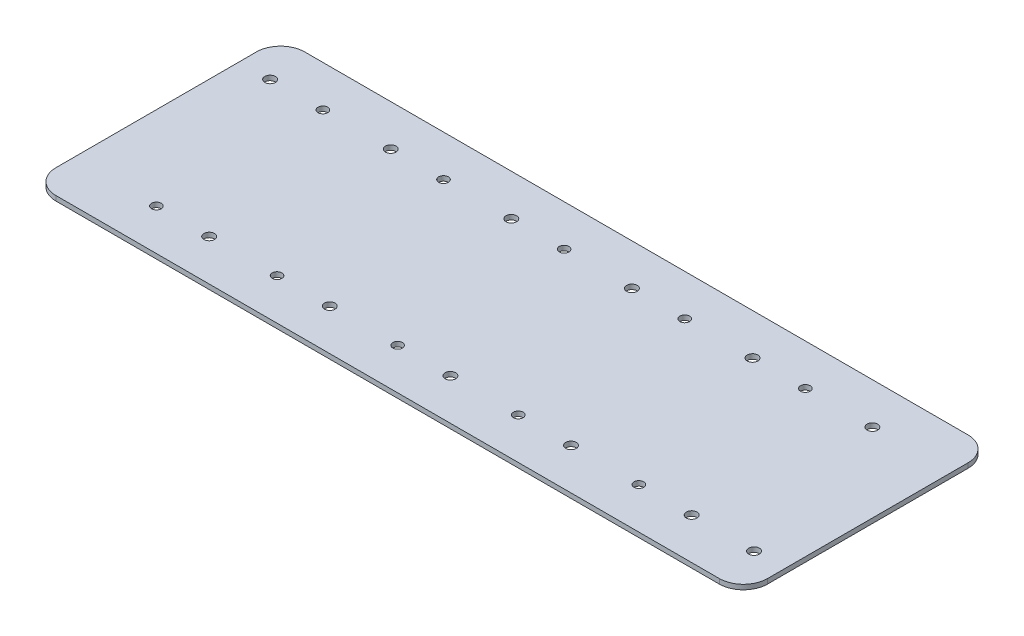
SolidWorks part; units mm, degrees
ref_plane "Front Plane" through (0, 0, 0) normal (0, 0, 1) x (1, 0, 0)
ref_plane "Top Plane" through (0, 0, 0) normal (0, 1, 0) x (1, 0, 0)
ref_plane "Right Plane" through (0, 0, 0) normal (1, 0, 0) x (0, 0, -1)
sketch "Sketch1" plane through (0, 0, 0) normal (0, 1, 0) x (1, 0, 0)
  line L1 (-118, -41.25) -> (118, -41.25)
  line L2 (-118, -41.25) -> (-118, 41.25)
  line L3 (-118, 41.25) -> (118, 41.25)
  line L4 (118, -41.25) -> (118, 41.25)
  line L5 (-118, -41.25) -> (118, 41.25) construction
  line L6 (-118, 41.25) -> (118, -41.25) construction
  point P0 (0, 0)
  dimension "D1" = 236
  dimension "D2" = 82.5
extrude "Boss-Extrude1" add sketch "Sketch1" along normal blind 1.6
fillet "Fillet1" radius 8 4 edges at (118, 0.8, -41.25) (118, 0.8, 41.25) (-118, 0.8, -41.25) (-118, 0.8, 41.25)
sketch "Sketch2" plane through (0, 1.6, 0) normal (0, 1, 0) x (1, 0, 0)
  circle A0 centre (-90.3251, 27.6) radius 1.6
  circle A1 centre (-90.3251, -27.6) radius 1.6
  circle A2 centre (-72.8251, -27.6) radius 1.75
  circle A3 centre (-107.8251, 27.6) radius 1.75
  circle A4 centre (-67.8251, 27.6) radius 1.75
  circle A5 centre (-50.3251, 27.6) radius 1.6
  circle A6 centre (-27.8251, 27.6) radius 1.75
  circle A7 centre (-10.3251, 27.6) radius 1.6
  circle A8 centre (12.1749, 27.6) radius 1.75
  circle A9 centre (29.6749, 27.6) radius 1.6
  circle A10 centre (52.1749, 27.6) radius 1.75
  circle A11 centre (-50.3251, -27.6) radius 1.6
  circle A12 centre (-32.8251, -27.6) radius 1.75
  circle A13 centre (-10.3251, -27.6) radius 1.6
  circle A14 centre (7.1749, -27.6) radius 1.75
  circle A15 centre (29.6749, -27.6) radius 1.6
  circle A16 centre (47.1749, -27.6) radius 1.75
  circle A17 centre (69.6749, -27.6) radius 1.6
  circle A18 centre (87.1749, -27.6) radius 1.75
  circle A19 centre (69.6749, 27.6) radius 1.6
  circle A20 centre (91.889, 27.6254) radius 1.75
  circle A21 centre (107.891, -27.6196) radius 1.75
  dimension "D1" = 3.2
  dimension "D2" = 3.5
extrude "Cut-Extrude1" cut sketch "Sketch2" against normal through all both and the other way through all
